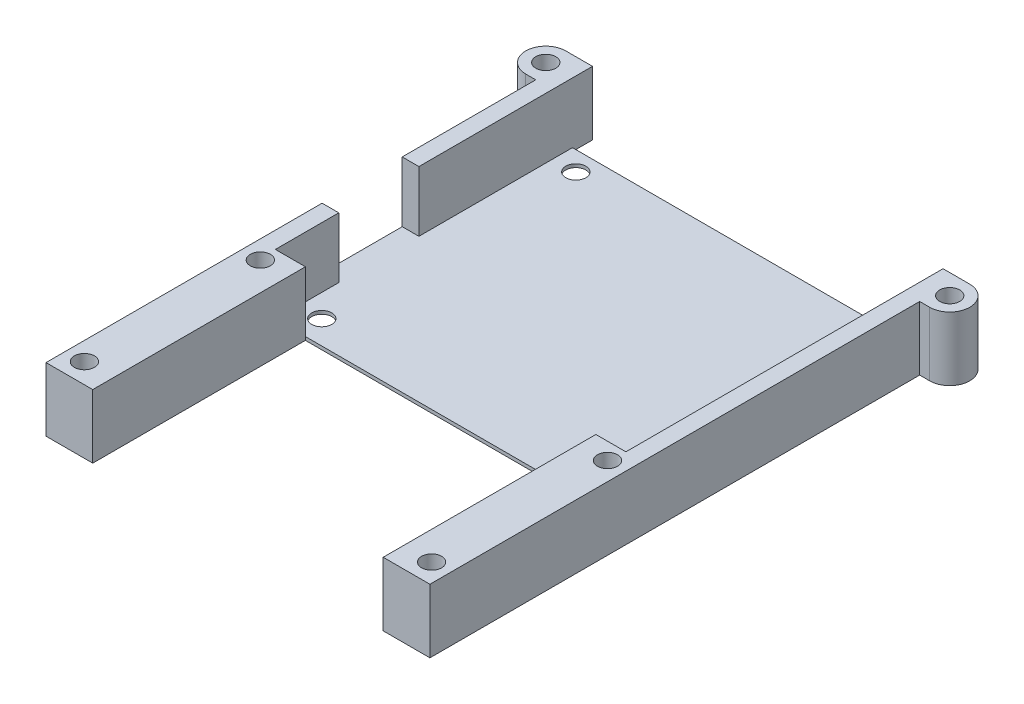
SolidWorks part; units mm, degrees
ref_plane "Front Plane" through (0, 0, 0) normal (0, 0, 1) x (1, 0, 0)
ref_plane "Top Plane" through (0, 0, 0) normal (0, 1, 0) x (1, 0, 0)
ref_plane "Right Plane" through (0, 0, 0) normal (1, 0, 0) x (0, 0, -1)
sketch "Sketch1" plane through (0, 0, 0) normal (0, 1, 0) x (1, 0, 0)
  line L0 (0, 0) -> (0, 76.35) construction
  line L1 (-28.75, 76.35) -> (28.75, 76.35)
  line L2 (28.75, 76.35) -> (28.75, 0)
  line L3 (28.75, 0) -> (21.75, 0)
  line L4 (21.75, 0) -> (21.75, 31.85)
  line L5 (21.75, 31.85) -> (-21.75, 31.85)
  line L6 (-21.75, 31.85) -> (-21.75, 0)
  line L7 (-21.75, 0) -> (-28.75, 0)
  line L8 (-28.75, 0) -> (-28.75, 76.35)
  line L9 (-26.25, 76.35) -> (-26.25, 31.85)
  line L14 (-26.25, 31.85) -> (-21.75, 31.85)
  line L15 (26.25, 76.35) -> (26.25, 31.85)
  line L16 (26.25, 31.85) -> (21.75, 31.85)
  line L17 (28.75, 79.35) -> (30.25, 79.35)
  line L18 (-28.75, 41.35) -> (-26.25, 41.35)
  line L19 (-28.75, 41.35) -> (-28.75, 53.35)
  line L20 (-28.75, 53.35) -> (-26.25, 53.35)
  line L21 (-26.25, 41.35) -> (-26.25, 53.35)
  line L22 (30.25, 73.35) -> (28.75, 73.35)
  line L23 (-30.25, 73.35) -> (-28.75, 73.35)
  line L24 (-28.75, 79.35) -> (-30.25, 79.35)
  line L25 (26.25, 76.35) -> (26.25, 79.35)
  line L26 (26.25, 79.35) -> (28.75, 79.35)
  line L28 (-28.75, 76.35) -> (-28.75, 79.35)
  line L29 (-28.75, 79.35) -> (-26.25, 79.35)
  line L30 (-26.25, 79.35) -> (-26.25, 76.35)
  arc A0 (30.25, 73.35) -> (30.25, 79.35) centre (30.25, 76.35) ccw
  arc A1 (-30.25, 73.35) -> (-30.25, 79.35) centre (-30.25, 76.35) cw
  point P10 (0, 76.35)
  point P16 (-27.5, 41.35)
  point P17 (-22.85, 73.45)
  point P18 (22.85, 73.45)
  point P23 (22.85, 35.4)
  point P24 (-22.85, 35.4)
  point P25 (26, 3)
  point P26 (26, 29.35)
  point P27 (-26, 29.35)
  point P28 (-26, 3)
  point P40 (30.25, 76.35)
  point P41 (-30.25, 76.35)
  dimension "D16" = 3
  dimension "D1" = 2.5
  dimension "D2" = 7
  dimension "D3" = 43.5
  dimension "D4" = 31.85
  dimension "D5" = 44.5
  dimension "D6" = 23
  dimension "D7" = 12
  dimension "D8" = 22.85
  dimension "D9" = 38.05
  dimension "D10" = 2.9
  dimension "D11" = 52
  dimension "D12" = 52
  dimension "D13" = 47
  dimension "D14" = 3
  dimension "D15" = 1.5
extrude "Boss-Extrude1" add sketch "Sketch1" along normal blind 0.5 contours L5 L0 L1 L9 L14 | L0 L5 L16 L15 L1 | L20 L8 L18 L9 region at (-13.125, 0, -54.1) region at (13.125, 0, -54.1) region at (-27.5, 0, -47.35)
extrude "Boss-Extrude2" add sketch "Sketch1<3>" along normal blind 9.55 contours L18 L8 L7 L6 L14 L9 | L8 L20 L9 L1 | L15 L16 L4 L3 L2 L1 | A1 L23 L8 L24 | L22 A0 L17 L2 | L26 L25 L1 | L30 L29 L28 L1 region at (-27.5, 0, -77.85) region at (-27.5, 0, -64.85) region at (-30.7362, 0, -76.35) region at (29.944, 0, -76.7172) region at (25.999, 0, -28.6329) region at (-25.4666, 0, -17.9154)
sketch "Sketch1<3>" plane through (0, 0, 0) normal (0, 1, 0) x (1, 0, 0) same geometry as "Sketch1"
hole_wizard "Ø3.0 (3) Diameter Hole1" positions "Sketch4" profile "Sketch5" hole size "Ø3.0" standard "ANSI Metric"
sketch "Sketch4" plane through (0, 0, 0) normal (0, -1, 0) x (-1, 0, 0)
  point P0 (-22.85, 73.45)
  point P3 (22.85, 73.45)
  point P6 (26, 29.35)
  point P9 (22.85, 35.4)
  point P12 (-22.85, 35.4)
  point P15 (-26, 29.35)
  point P18 (-26, 3)
  point P21 (26, 3)
  point P24 (-30.25, 76.35)
  point P27 (30.25, 76.35)
sketch "Sketch5" plane through (22.85, 0, -73.45) normal (1, 0, 0) x (0, 0, -1)
  line L0 (0, 0) -> (0, 12.9013)
  line L1 (0, 12.9013) -> (1.5, 12)
  line L2 (1.5, 12) -> (1.5, 0)
  line L5 (1.5, 0) -> (0, 0)
  line L10 (0, 12.9013) -> (-1.5, 12) construction
  line L11 (0, -6.35) -> (0, 107.95) construction
  dimension "Hole Dia." = 3
  dimension "Hole Depth" = 12
  dimension "Drill Angle" = 118
